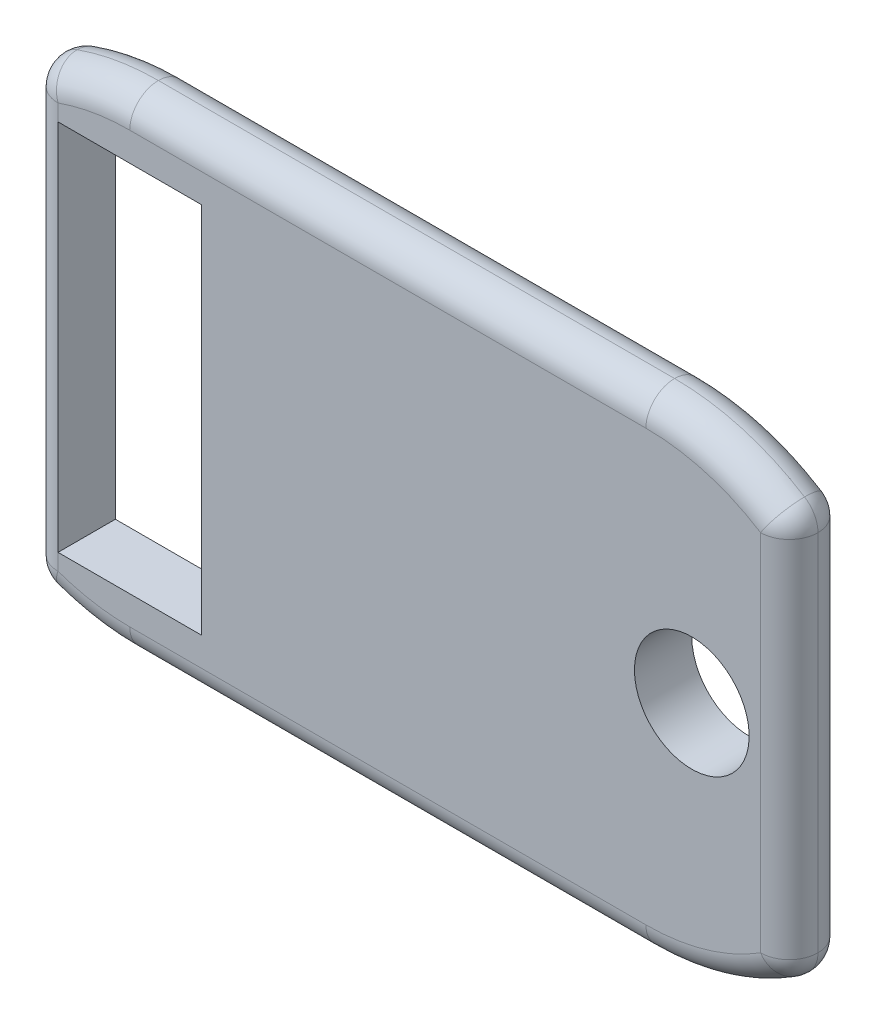
SolidWorks part; units mm, degrees
ref_plane "Front Plane" through (0, 0, 0) normal (0, 0, 1) x (1, 0, 0)
ref_plane "Top Plane" through (0, 0, 0) normal (0, 1, 0) x (1, 0, 0)
ref_plane "Right Plane" through (0, 0, 0) normal (1, 0, 0) x (0, 0, -1)
sketch "Sketch1" plane through (0, 0, 0) normal (0, 0, 1) x (1, 0, 0)
  line L1 (-51.3243, 15.0309) -> (38.6757, 15.0309)
  line L2 (38.6757, 15.0309) -> (38.6757, -69.9691) construction
  line L3 (38.6757, -69.9691) -> (-51.3243, -69.9691)
  line L5 (-68.8243, -66.1989) -> (-68.8243, 11.2608)
  line L6 (63.6757, -61.8384) -> (63.6757, 6.9003)
  arc A0 (-51.3243, 15.0309) -> (-68.8243, 11.2608) centre (-51.3243, -27.4691) ccw
  arc A2 (38.6757, 15.0309) -> (63.6757, 6.9003) centre (38.6757, -27.4691) cw
  arc A3 (-68.8243, -66.1989) -> (-51.3243, -69.9691) centre (-51.3243, -27.4691) ccw
  arc A4 (63.6757, -61.8384) -> (38.6757, -69.9691) centre (38.6757, -27.4691) cw
  dimension "D1" = 90
  dimension "D2" = 25
  dimension "D3" = 17.5
extrude "Boss-Extrude1" add sketch "Sketch1" along normal blind 10
sketch "Sketch2" plane through (0, 0, 0) normal (0, 0, -1) x (-1, 0, 0)
  line L0 (51.3243, 15.0309) -> (51.3243, 5.0309) construction
  line L6 (51.3243, 5.0309) -> (51.3243, -59.9691) construction
  line L8 (38.8243, -59.9691) -> (63.8243, -59.9691)
  line L9 (38.8243, -59.9691) -> (38.8243, 5.0309)
  line L10 (38.8243, 5.0309) -> (63.8243, 5.0309)
  line L11 (63.8243, -59.9691) -> (63.8243, 5.0309)
  line L12 (38.8243, -59.9691) -> (63.8243, 5.0309) construction
  line L13 (38.8243, 5.0309) -> (63.8243, -59.9691) construction
  point P7 (51.3243, -27.4691)
extrude "Cut-Extrude2" cut sketch "Sketch2" against normal blind 20
sketch "Sketch3" plane through (0, 0, 0) normal (0, 0, -1) x (-1, 0, 0)
  line L0 (-63.6757, -61.8384) -> (-63.6757, 6.9003) construction
  circle A0 centre (-46.6757, -27.4691) radius 10
  dimension "D1" = 17
extrude "Cut-Extrude3" cut sketch "Sketch3" against normal blind 20
fillet "Fillet2" radius 5 16 edges at (-60.275, -69.0158, 10) (-60.275, -69.0158, 0) (-6.3243, -69.9691, 10) (-6.3243, -69.9691, 0) (51.8202, -67.8853, 10) (51.8202, -67.8853, 0) (63.6757, -27.4691, 10) (63.6757, -27.4691, 0) (51.8202, 12.9472, 10) (51.8202, 12.9472, 0) (-68.8243, -27.4691, 10) (-68.8243, -27.4691, 0) (-6.3243, 15.0309, 10) (-6.3243, 15.0309, 0) (-60.275, 14.0777, 10) (-60.275, 14.0777, 0)
